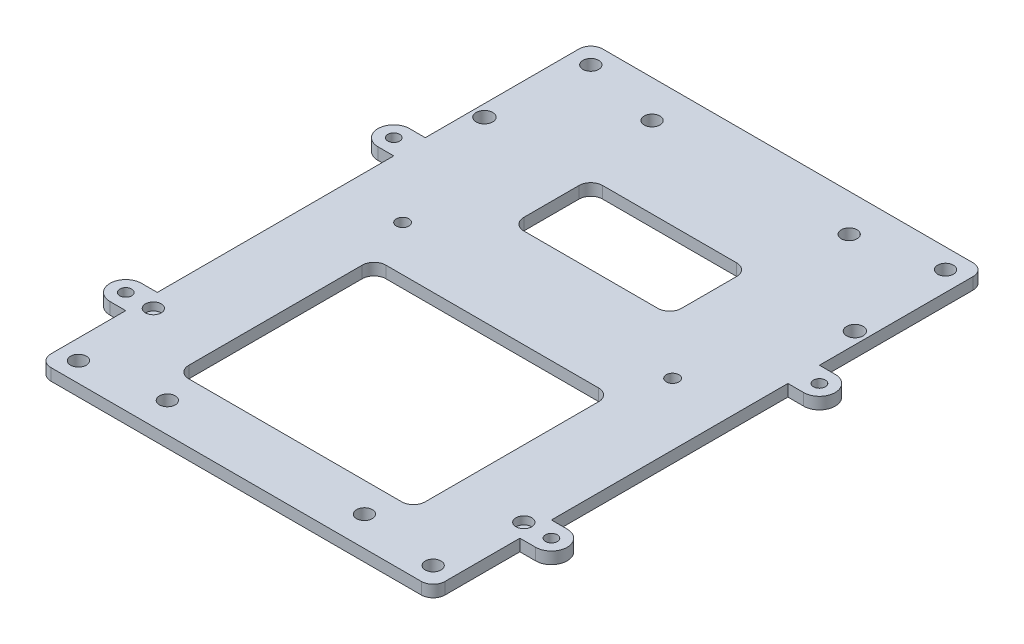
SolidWorks part; units mm, degrees
ref_plane "前视基准面" through (0, 0, 0) normal (0, 0, 1) x (1, 0, 0)
ref_plane "上视基准面" through (0, 0, 0) normal (0, 1, 0) x (1, 0, 0)
ref_plane "右视基准面" through (0, 0, 0) normal (1, 0, 0) x (0, 0, -1)
sketch "Sketch1" plane through (0, 0, 0) normal (0, 1, 0) x (1, 0, 0)
  line L0 (0, 0) -> (69620.7582, 0) construction
  line L5 (0, 0) -> (0, -69620.7582) construction
  line L7 (-50, 70) -> (50, 70)
  line L8 (-50, 70) -> (-50, -70)
  line L9 (-50, -70) -> (50, -70)
  line L10 (50, 70) -> (50, -70)
  line L11 (-50, 70) -> (50, -70) construction
  line L12 (-50, -70) -> (50, 70) construction
  circle A0 centre (45, 65) radius 2
  circle A1 centre (-45, 65) radius 2
  circle A2 centre (-45, -65) radius 2
  circle A3 centre (45, -65) radius 2
  point P14 (0, 0)
  dimension "D3" = 4
  dimension "D4" = 5
  dimension "D5" = 5
  dimension "D1" = 90
  dimension "D2" = 130
extrude "Extrude1" add sketch "Sketch1" along normal blind 2
sketch "Sketch2" plane through (0, 2, 0) normal (0, 1, 0) x (1, 0, 0)
  line L1 (-30, -55) -> (30, -55)
  line L2 (-30, -55) -> (-30, -5)
  line L3 (-30, -5) -> (30, -5)
  line L4 (30, -55) -> (30, -5)
  line L5 (-30, -55) -> (30, -5) construction
  line L6 (-30, -5) -> (30, -55) construction
  point P0 (0, -30)
  dimension "D1" = 30
  dimension "D2" = 50
  dimension "D3" = 60
extrude "Extrude2" cut sketch "Sketch2" against normal through all
sketch "Sketch3" plane through (0, 2, 0) normal (0, 1, 0) x (1, 0, 0)
  line L0 (30, -5) -> (-30, -5) construction
  line L1 (20, 40) -> (-20, 40)
  line L2 (20, 40) -> (20, 20)
  line L3 (20, 20) -> (-20, 20)
  line L4 (-20, 40) -> (-20, 20)
  line L5 (20, 40) -> (-20, 20) construction
  line L6 (20, 20) -> (-20, 40) construction
  point P0 (0, 30)
  dimension "D1" = 20
  dimension "D2" = 40
  dimension "D3" = 35
extrude "Extrude3" cut sketch "Sketch3" against normal through all
fillet "Fillet1" radius 3 12 edges at (50, 1, 70) (-50, 1, 70) (-50, 1, -70) (30, 1, 5) (-30, 1, 5) (-30, 1, 55) (30, 1, 55) (-20, 1, -20) (20, 1, -20) (20, 1, -40) (-20, 1, -40) (50, 1, -70)
sketch "Sketch4" plane through (0, 0, 0) normal (0, -1, 0) x (1, 0, 0)
  line L0 (0, 0) -> (0, 50000) construction
  line L1 (50, 67) -> (50, -67) construction
  line L2 (50, 40) -> (44, 40)
  line L3 (50, 40) -> (50, 48)
  line L4 (50, 48) -> (44, 48)
  line L5 (44, 40) -> (44, 48)
  line L6 (0, 0) -> (50000, 0) construction
  line L7 (50, -28) -> (44, -28)
  line L8 (50, -28) -> (50, -20)
  line L9 (50, -20) -> (44, -20)
  line L10 (44, -28) -> (44, -20)
  line L11 (-44, -28) -> (-44, -20)
  line L12 (-50, -20) -> (-44, -20)
  line L13 (-50, -28) -> (-50, -20)
  line L14 (-50, -28) -> (-44, -28)
  line L15 (-44, 40) -> (-44, 48)
  line L16 (-50, 48) -> (-44, 48)
  line L17 (-50, 40) -> (-50, 48)
  line L18 (-50, 40) -> (-44, 40)
  dimension "D1" = 8
  dimension "D2" = 6
  dimension "D3" = 8
  dimension "D4" = 6
  dimension "D5" = 40
  dimension "D6" = 20
extrude "Extrude4" add sketch "Sketch4" along normal blind 60
sketch "Sketch5" plane through (0, -60, 0) normal (0, -1, 0) x (1, 0, 0)
  line L0 (44, 40) -> (44, 48)
  line L1 (44, 48) -> (54, 48)
  line L2 (54, 40) -> (44, 40)
  line L3 (44, -28) -> (44, -20)
  line L4 (44, -20) -> (54, -20)
  line L5 (54, -28) -> (44, -28)
  line L6 (0, 0) -> (0, -50000) construction
  line L7 (-44, -20) -> (-54, -20)
  line L8 (-44, -28) -> (-44, -20)
  line L9 (-54, -28) -> (-44, -28)
  line L10 (-44, 48) -> (-54, 48)
  line L11 (-44, 40) -> (-44, 48)
  line L12 (-54, 40) -> (-44, 40)
  arc A0 (54, 48) -> (54, 40) centre (54, 44) cw
  arc A1 (54, -20) -> (54, -28) centre (54, -24) cw
  circle A2 centre (54, 44) radius 1
  circle A3 centre (54, -24) radius 1
  circle A4 centre (-54, -24) radius 1
  arc A5 (-54, -20) -> (-54, -28) centre (-54, -24) ccw
  circle A6 centre (-54, 44) radius 1
  arc A7 (-54, 48) -> (-54, 40) centre (-54, 44) ccw
  dimension "D3" = 2
  dimension "D4" = 2
  dimension "D1" = 10
  dimension "D2" = 10
extrude "Extrude5" add sketch "Sketch5" against normal blind 8
sketch "Sketch6" plane through (0, 0, 0) normal (0, -1, 0) x (-1, 0, 0)
  line L0 (-38.4787, -70) -> (-38.4787, -44) construction
  line L1 (47, -70) -> (-47, -70) construction
  line L2 (-47, -44) -> (-50, -44) construction
  line L3 (-50, -67) -> (-50, -48) construction
  line L4 (-50, -44) -> (-47, -44) construction
  line L5 (0, 70) -> (0, -143.2461) construction
  line L6 (-47, 70) -> (47, 70) construction
  line L7 (-50, 40) -> (-47, 40) construction
  line L8 (-47, 70) -> (47, 70) construction
  line L9 (50, 40) -> (47, 40) construction
  line L10 (50, -44) -> (47, -44) construction
  line L11 (47, -44) -> (50, -44) construction
  circle A0 centre (-47, -44) radius 2
  circle A1 centre (-47, 40) radius 2.1
  circle A2 centre (47, 40) radius 2.1
  circle A3 centre (47, -44) radius 2
  dimension "D2" = 4
  dimension "D4" = 4.2
  dimension "D5" = 30
  dimension "D1" = 3
  dimension "D3" = 3
extrude "Extrude6" cut sketch "Sketch6" against normal blind 10
sketch "Sketch8" plane through (0, 2, 0) normal (0, 1, 0) x (1, 0, 0)
  line L0 (40, 70) -> (40, 35) construction
  line L1 (40, 24.75) -> (40, 14.75) construction
  line L11 (0, 70) -> (0, 0) construction
  line L12 (47, 70) -> (-47, 70) construction
  line L13 (50, 70) -> (40, 70) construction
  line L25 (40, 19.75) -> (53.0368, 19.75) construction
  line L30 (50, -67) -> (50, 67) construction
  line L31 (30, 16.25) -> (50, 16.25)
  line L32 (30, 16.25) -> (30, 23.25)
  line L33 (30, 23.25) -> (50, 23.25)
  line L34 (50, 16.25) -> (50, 23.25)
  line L35 (30, 16.25) -> (50, 23.25) construction
  line L36 (30, 23.25) -> (50, 16.25) construction
  line L38 (43.25, 35) -> (36.75, 35)
  line L39 (45.25, 35) -> (45.25, 32.5)
  line L40 (43.25, 32.5) -> (36.75, 32.5)
  line L41 (34.75, 35) -> (34.75, 32.5)
  line L45 (34.75, 4.5) -> (34.75, 7)
  line L46 (43.25, 7) -> (36.75, 7)
  line L47 (45.25, 4.5) -> (45.25, 7)
  line L48 (43.25, 4.5) -> (36.75, 4.5)
  arc A27 (43.25, 4.5) -> (45.25, 4.5) centre (44.25, 4.5) ccw
  arc A28 (45.25, 7) -> (43.25, 7) centre (44.25, 7) ccw
  arc A29 (34.75, 4.5) -> (36.75, 4.5) centre (35.75, 4.5) ccw
  arc A30 (36.75, 7) -> (34.75, 7) centre (35.75, 7) ccw
  arc A31 (36.75, 32.5) -> (34.75, 32.5) centre (35.75, 32.5) cw
  arc A32 (34.75, 35) -> (36.75, 35) centre (35.75, 35) cw
  arc A33 (45.25, 32.5) -> (43.25, 32.5) centre (44.25, 32.5) cw
  arc A34 (43.25, 35) -> (45.25, 35) centre (44.25, 35) cw
  point P0 (45.25, 24.75)
  point P24 (34.75, 24.75)
  point P38 (40, 35)
  dimension "D4" = 2.5
  dimension "D5" = 2
  dimension "D9" = 2.5
  dimension "D10" = 6.5
  dimension "D6" = 10
  dimension "D7" = 2
  dimension "D8" = 1
  dimension "D2" = 35
  dimension "D3" = 10.5
  dimension "D1" = 10
  dimension "D11" = 6.5
ref_plane "Plane1" through (0, 0, 0) normal (-1, 0, 0) x (0, 0, 1)
sketch "草图3" plane through (0, 2, 0) normal (0, 1, 0) x (1, 0, 0)
  line L0 (50, 28) -> (50, 20) construction
  line L1 (50, 20) -> (54, 20) construction
  line L2 (54, 28) -> (50, 28) construction
  line L3 (50, -40) -> (50, -48) construction
  line L4 (50, -48) -> (54, -48) construction
  line L5 (54, -40) -> (50, -40) construction
  line L6 (-54, -48) -> (-50, -48) construction
  line L7 (-50, -48) -> (-50, -40) construction
  line L8 (-50, -40) -> (-54, -40) construction
  line L9 (-50, 20) -> (-50, 28) construction
  line L10 (-54, 28) -> (-50, 28) construction
  line L11 (-50, 20) -> (-54, 20) construction
  line L12 (50, 28) -> (50, 20)
  line L13 (50, 20) -> (54, 20)
  line L14 (54, 28) -> (50, 28)
  line L15 (50, -40) -> (50, -48)
  line L16 (50, -48) -> (54, -48)
  line L17 (54, -40) -> (50, -40)
  line L18 (-54, -48) -> (-50, -48)
  line L19 (-50, -48) -> (-50, -40)
  line L20 (-50, -40) -> (-54, -40)
  line L21 (-50, 20) -> (-50, 28)
  line L22 (-54, 28) -> (-50, 28)
  line L23 (-50, 20) -> (-54, 20)
  arc A0 (54, 20) -> (54, 28) centre (54, 24) ccw construction
  arc A1 (54, -48) -> (54, -40) centre (54, -44) ccw construction
  arc A2 (-54, -40) -> (-54, -48) centre (-54, -44) ccw construction
  arc A3 (-54, 28) -> (-54, 20) centre (-54, 24) ccw construction
  arc A4 (54, 20) -> (54, 28) centre (54, 24) ccw
  arc A5 (54, -48) -> (54, -40) centre (54, -44) ccw
  arc A6 (-54, -40) -> (-54, -48) centre (-54, -44) ccw
  arc A7 (-54, 28) -> (-54, 20) centre (-54, 24) ccw
  circle A8 centre (-54, 24) radius 1.5
  circle A10 centre (-54, -44) radius 1.5
  circle A11 centre (54, -44) radius 1.5
  circle A12 centre (54, 24) radius 1.5
  dimension "D1" = 3
  dimension "D2" = 3
  dimension "D3" = 3
  dimension "D4" = 3
extrude "凸台-拉伸1" add sketch "草图3" against normal blind 3
sketch "草图4" plane through (50, 0, 0) normal (1, 0, 0) x (0, 0, -1)
  line L1 (-48, -1) -> (55.958, -1)
  line L2 (-48, -1) -> (-48, -75.1501)
  line L3 (-48, -75.1501) -> (55.958, -75.1501)
  line L4 (55.958, -1) -> (55.958, -75.1501)
extrude "切除-拉伸3" cut sketch "草图4" against normal blind 134 and the other way blind 29
sketch "草图6" plane through (0, 2, 0) normal (0, 1, 0) x (1, 0, 0)
  line L0 (-50, 60.55) -> (-25, 60.55) construction
  line L1 (-50, 67) -> (-50, 28) construction
  line L2 (47, 70) -> (-47, 70) construction
  line L3 (0, 60.55) -> (0, 70) construction
  line L4 (0, 1.1) -> (0, -1.1) construction
  circle A0 centre (-25, 60.55) radius 2
  circle A1 centre (25, 60.55) radius 2
  dimension "D1" = 9.45
  dimension "D2" = 4
  dimension "D3" = 25
extrude "切除-拉伸4" cut sketch "草图6" against normal blind 11
sketch "草图8" plane through (0, 0, 0) normal (0, -1, 0) x (-1, 0, 0)
  line L0 (47, -70) -> (-47, -70) construction
  line L1 (50, -48) -> (50, -67) construction
  line L2 (0, -64.24) -> (0, -60.263) construction
  line L3 (0, -1.1) -> (0, 1.1) construction
  circle A0 centre (25, -62.44) radius 2
  circle A1 centre (-25, -62.44) radius 2
  dimension "D1" = 7.56
  dimension "D2" = 25
  dimension "D3" = 4
extrude "切除-拉伸6" cut sketch "草图8" against normal blind 11
sketch "草图9" plane through (0, 0, 0) normal (0, -1, 0) x (1, 0, 0)
  line L0 (30, 52) -> (30, 8) construction
  line L1 (27, 5) -> (-27, 5) construction
  line L2 (-30, 8) -> (-30, 52) construction
  line L3 (-27, 55) -> (27, 55) construction
  line L4 (20, -23) -> (20, -37) construction
  line L5 (17, -40) -> (-17, -40) construction
  line L6 (-20, -37) -> (-20, -23) construction
  line L7 (-17, -20) -> (17, -20) construction
  line L8 (30, 52) -> (30, 8)
  line L9 (27, 5) -> (-27, 5)
  line L10 (-30, 8) -> (-30, 52)
  line L11 (-27, 55) -> (27, 55)
  line L12 (20, -23) -> (20, -37)
  line L13 (17, -40) -> (-17, -40)
  line L14 (-20, -37) -> (-20, -23)
  line L15 (-17, -20) -> (17, -20)
  line L20 (-44, 40) -> (-50, 40)
  line L21 (-50, 40) -> (-50, -20)
  line L22 (-50, -20) -> (-44, -20)
  line L23 (-44, -20) -> (-44, -28)
  line L24 (-44, -28) -> (-50, -28)
  line L25 (-50, -28) -> (-50, -67)
  line L26 (-47, -70) -> (47, -70)
  line L27 (50, -67) -> (50, -28)
  line L28 (50, -28) -> (44, -28)
  line L29 (44, -28) -> (44, -20)
  line L30 (44, -20) -> (50, -20)
  line L31 (50, -20) -> (50, 40)
  line L32 (50, 40) -> (44, 40)
  line L33 (44, 40) -> (44, 48)
  line L34 (44, 48) -> (50, 48)
  line L35 (50, 48) -> (50, 67)
  line L36 (47, 70) -> (-47, 70)
  line L37 (-50, 67) -> (-50, 48)
  line L38 (-50, 48) -> (-44, 48)
  line L39 (-44, 48) -> (-44, 40)
  line L40 (-44, 40) -> (-50, 40)
  line L41 (-50, 40) -> (-50, -20)
  line L42 (-50, -20) -> (-44, -20)
  line L43 (-44, -20) -> (-44, -28)
  line L44 (-44, -28) -> (-50, -28)
  line L45 (-50, -28) -> (-50, -67)
  line L46 (-47, -70) -> (47, -70)
  line L47 (50, -67) -> (50, -28)
  line L48 (50, -28) -> (44, -28)
  line L49 (44, -28) -> (44, -20)
  line L50 (44, -20) -> (50, -20)
  line L51 (50, -20) -> (50, 40)
  line L52 (50, 40) -> (44, 40)
  line L53 (44, 40) -> (44, 48)
  line L54 (44, 48) -> (50, 48)
  line L55 (50, 48) -> (50, 67)
  line L56 (47, 70) -> (-47, 70)
  line L57 (-50, 67) -> (-50, 48)
  line L58 (-50, 48) -> (-44, 48)
  line L59 (-44, 48) -> (-44, 40)
  circle A0 centre (-45, 65) radius 2 construction
  circle A1 centre (-25, 62.44) radius 2 construction
  circle A2 centre (45, 65) radius 2 construction
  circle A3 centre (25, 62.44) radius 2 construction
  arc A4 (-50, -67) -> (-47, -70) centre (-47, -67) ccw
  arc A5 (47, -70) -> (50, -67) centre (47, -67) ccw
  arc A6 (50, 67) -> (47, 70) centre (47, 67) ccw
  arc A7 (-47, 70) -> (-50, 67) centre (-47, 67) ccw
  arc A8 (-50, -67) -> (-47, -70) centre (-47, -67) ccw
  arc A9 (47, -70) -> (50, -67) centre (47, -67) ccw
  arc A10 (50, 67) -> (47, 70) centre (47, 67) ccw
  arc A11 (-47, 70) -> (-50, 67) centre (-47, 67) ccw
  arc A12 (30, 52) -> (27, 55) centre (27, 52) ccw construction
  arc A13 (27, 5) -> (30, 8) centre (27, 8) ccw construction
  arc A14 (-30, 8) -> (-27, 5) centre (-27, 8) ccw construction
  arc A15 (-27, 55) -> (-30, 52) centre (-27, 52) ccw construction
  circle A16 centre (47, -40) radius 2.1 construction
  circle A17 centre (45, -65) radius 2 construction
  circle A18 centre (25, -60.55) radius 2 construction
  circle A19 centre (-45, -65) radius 2 construction
  circle A20 centre (-47, -40) radius 2.1 construction
  circle A21 centre (-25, -60.55) radius 2 construction
  arc A22 (-20, -37) -> (-17, -40) centre (-17, -37) ccw construction
  arc A23 (20, -23) -> (17, -20) centre (17, -23) ccw construction
  arc A24 (17, -40) -> (20, -37) centre (17, -37) ccw construction
  arc A25 (-17, -20) -> (-20, -23) centre (-17, -23) ccw construction
  circle A26 centre (-45, 65) radius 2
  circle A27 centre (-25, 62.44) radius 2
  circle A28 centre (45, 65) radius 2
  circle A29 centre (25, 62.44) radius 2
  arc A30 (30, 52) -> (27, 55) centre (27, 52) ccw
  arc A31 (27, 5) -> (30, 8) centre (27, 8) ccw
  arc A32 (-30, 8) -> (-27, 5) centre (-27, 8) ccw
  arc A33 (-27, 55) -> (-30, 52) centre (-27, 52) ccw
  circle A34 centre (47, -40) radius 2.1
  circle A35 centre (45, -65) radius 2
  circle A36 centre (25, -60.55) radius 2
  circle A37 centre (-45, -65) radius 2
  circle A38 centre (-47, -40) radius 2.1
  circle A39 centre (-25, -60.55) radius 2
  arc A40 (-20, -37) -> (-17, -40) centre (-17, -37) ccw
  arc A41 (20, -23) -> (17, -20) centre (17, -23) ccw
  arc A42 (17, -40) -> (20, -37) centre (17, -37) ccw
  arc A43 (-17, -20) -> (-20, -23) centre (-17, -23) ccw
  dimension "D1" = 0
extrude "凸台-拉伸2" add sketch "草图9" along normal blind 1
sketch "草图10" plane through (0, -1, 0) normal (0, -1, 0) x (-1, 0, 0)
  line L0 (50, 6.5) -> (34.25, 6.5) construction
  line L1 (50, -40) -> (50, 20) construction
  line L2 (-47, -70) -> (47, -70) construction
  line L3 (0, -70) -> (0, 70.4837) construction
  line L4 (0, -1.65) -> (0, 1.65) construction
  line L5 (-50, 6.5) -> (-34.25, 6.5) construction
  circle A0 centre (34.25, 6.5) radius 1.6
  circle A1 centre (-34.25, 6.5) radius 1.6
  dimension "D1" = 3.2
  dimension "D2" = 76.5
extrude "切除-拉伸7" cut sketch "草图10" against normal blind 3
